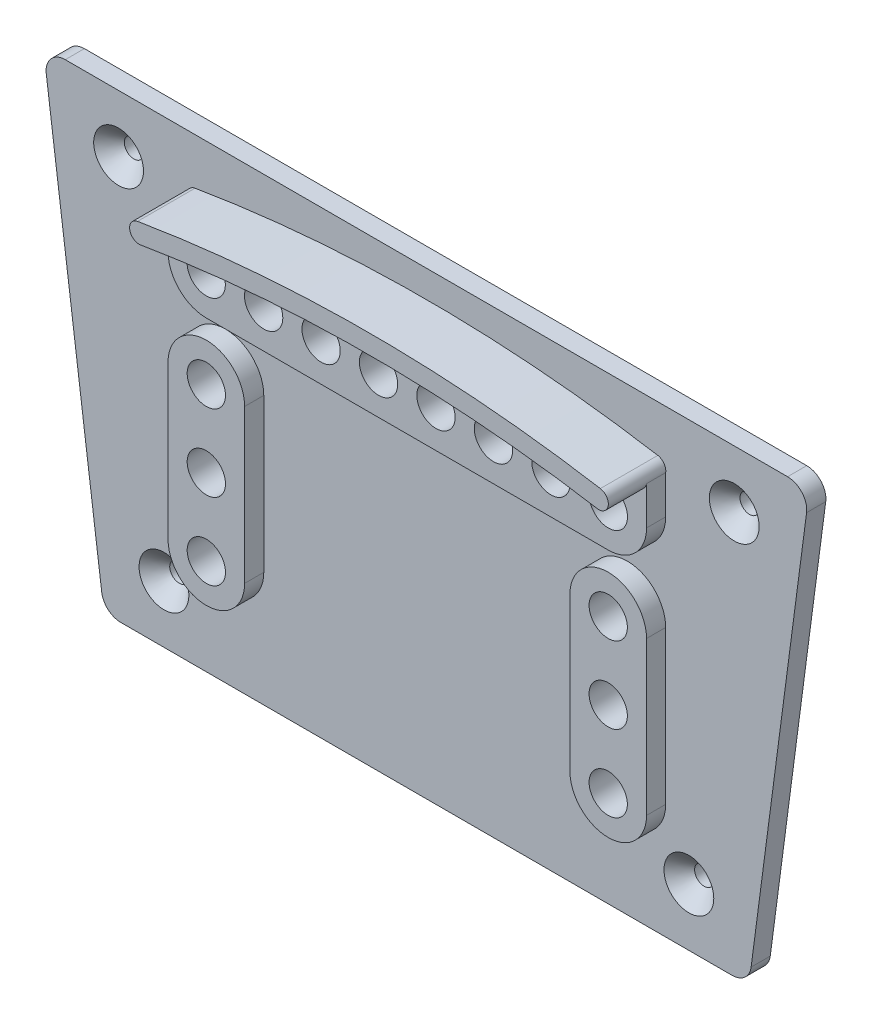
SolidWorks part; units mm, degrees
material "Nylon 101"
ref_plane "Front Plane" through (0, 0, 0) normal (0, 0, 1) x (1, 0, 0)
ref_plane "Top Plane" through (0, 0, 0) normal (0, 1, 0) x (1, 0, 0)
ref_plane "Right Plane" through (0, 0, 0) normal (1, 0, 0) x (0, 0, -1)
sketch "Sketch1" plane through (0, 0, 0) normal (0, 0, 1) x (1, 0, 0)
  line L1 (-53.4681, -38.1) -> (53.4681, -38.1)
  line L2 (-53.4681, -38.1) -> (-63.5, 38.1)
  line L3 (-63.5, 38.1) -> (63.5, 38.1)
  line L4 (53.4681, -38.1) -> (63.5, 38.1)
  line L5 (0, 38.1) -> (0, -38.1) construction
  line L6 (-58.484, 0) -> (58.484, 0) construction
  line L7 (-47.8993, -31.75) -> (47.8993, -31.75)
  line L8 (-47.8993, -31.75) -> (-56.2592, 31.75)
  line L9 (-56.2592, 31.75) -> (56.2592, 31.75)
  line L10 (47.8993, -31.75) -> (56.2592, 31.75)
  line L11 (0, 31.75) -> (0, -31.75) construction
  line L12 (-52.0792, 0) -> (52.0792, 0) construction
  point P0 (0, 0)
  point P4 (0, 0)
  dimension "D1" = 127
  dimension "D2" = 76.2
  dimension "D3" = 6.35
  dimension "D4" = 6.35
  dimension "D5" = 15
extrude "Boss-Extrude1" add sketch "Sketch1" along normal blind 3.175 contours L7 L10 L9 L8 | L1 L4 L3 L2 L10 L7 L8 L9 region at (-57.0156, 0.1933, 0) region at (0, 0.8494, 0)
extrude "Boss-Extrude2" add sketch "Sketch1<3>" against normal blind 3.175 contours L7 L10 L9 L8 region at (0, 0.8494, 0)
sketch "Sketch1<3>" plane through (0, 0, 0) normal (0, 0, 1) x (1, 0, 0) same geometry as "Sketch1"
sketch "Sketch2" plane through (0, 0, 0) normal (0, 0, 1) x (1, 0, 0)
  line L0 (-38.1, 28.8378) -> (0, 0) construction
  line L2 (0, 0) -> (38.1, 28.8378) construction
  line L4 (-33.3375, 22.225) -> (-23.8125, 22.225) construction
  line L5 (-39.6656, 28.575) -> (39.6656, 28.575) construction
  line L6 (-39.6656, 28.575) -> (-39.6656, 15.875)
  line L7 (-39.6656, 15.875) -> (39.6656, 15.875)
  line L8 (39.6656, 28.575) -> (39.6656, 15.875)
  line L9 (0, 22.225) -> (0, 0) construction
  line L10 (-33.3375, 22.225) -> (33.3375, 22.225) construction
  line L11 (-63.5, 38.1) -> (63.5, 38.1) construction
  arc A5 (-38.1, 28.8378) -> (38.1, 28.8378) centre (0, -198.1747) cw construction
  arc A6 (-37.8372, 27.2722) -> (37.8372, 27.2722) centre (0, -198.1747) cw
  arc A7 (-38.3628, 30.4034) -> (38.3628, 30.4034) centre (0, -198.1747) cw
  arc A8 (-37.8372, 27.2722) -> (-38.3628, 30.4034) centre (-38.1, 28.8378) cw
  arc A9 (37.8372, 27.2722) -> (38.3628, 30.4034) centre (38.1, 28.8378) ccw
  circle A10 centre (-33.3375, 22.225) radius 3.175
  circle A11 centre (-23.8125, 22.225) radius 3.175
  circle A12 centre (-14.2875, 22.225) radius 3.175
  circle A13 centre (-4.7625, 22.225) radius 3.175
  circle A14 centre (4.7625, 22.225) radius 3.175
  circle A15 centre (14.2875, 22.225) radius 3.175
  circle A16 centre (23.8125, 22.225) radius 3.175
  circle A17 centre (33.3375, 22.225) radius 3.175
  point P7 (0, 22.225)
  point P8 (39.6656, 22.225)
  point P9 (0, 32.0128)
  dimension "D1" = 15.875
  dimension "D3" = 3.175
  dimension "D4" = 1.5875
  dimension "D7" = 6.35
  dimension "D8" = 8
  dimension "D5" = 1.5875
  dimension "D2" = 76.2
  dimension "D6" = 12.7
  dimension "D9" = 9.525
extrude "Boss-Extrude3" add sketch "Sketch2" along normal blind 6.35 contours A9 A6 A8 L6 L7 L8 A17 A16 A15 A14 A13 A12 A11 A10 | A10 | A11 | A12 | A13 | A14 | A15 | A16 | A17 | A6 A9 A7 A8 region at (0, 22.7442, 0) region at (0, 30.8867, 0) region at (-33.3375, 22.225, 0) region at (-23.8125, 22.225, 0) region at (-14.2875, 22.225, 0) region at (-4.7625, 22.225, 0) region at (4.7625, 22.225, 0) region at (14.2875, 22.225, 0) region at (23.8125, 22.225, 0) region at (33.3375, 22.225, 0)
extrude "Boss-Extrude4" add sketch "Sketch2<3>" along normal blind 12.7 contours A6 A9 A7 A8 region at (0, 30.8867, 0)
sketch "Sketch2<3>" plane through (0, 0, 0) normal (0, 0, 1) x (1, 0, 0) same geometry as "Sketch2"
extrude "Cut-Extrude1" cut sketch "Sketch2<4>" against normal through all both and the other way through all contours A10 | A11 | A12 | A13 | A14 | A15 | A16 | A17 region at (-33.3375, 22.225, 0) region at (-23.8125, 22.225, 0) region at (-14.2875, 22.225, 0) region at (-4.7625, 22.225, 0) region at (4.7625, 22.225, 0) region at (14.2875, 22.225, 0) region at (23.8125, 22.225, 0) region at (33.3375, 22.225, 0)
sketch "Sketch2<4>" plane through (0, 0, 0) normal (0, 0, 1) x (1, 0, 0) same geometry as "Sketch2"
fillet "Fillet1" radius 6.35 2 edges at (39.6656, 15.875, 4.7625) (-39.6656, 15.875, 4.7625)
sketch "Sketch4" plane through (0, 0, 0) normal (0, 0, 1) x (1, 0, 0)
  line L0 (0, 0) -> (0, -19.05) construction
  line L1 (-33.3156, 6.35) -> (33.3156, 6.35) construction
  line L2 (-33.3156, 6.35) -> (-33.3156, -19.05) construction
  line L3 (-33.3156, -19.05) -> (33.3156, -19.05) construction
  line L4 (33.3156, 6.35) -> (33.3156, -19.05) construction
  line L5 (-63.5, 38.1) -> (63.5, 38.1) construction
  line L6 (-33.3156, 6.35) -> (-33.3156, -19.05) construction
  line L7 (-26.9656, 6.35) -> (-26.9656, -19.05)
  line L8 (-39.6656, 6.35) -> (-39.6656, -19.05)
  line L9 (33.3156, 6.35) -> (33.3156, -19.05) construction
  line L10 (39.6656, 6.35) -> (39.6656, -19.05)
  line L11 (26.9656, 6.35) -> (26.9656, -19.05)
  line L12 (-39.6656, 22.225) -> (-39.6656, 28.575) construction
  circle A0 centre (-33.3156, 6.35) radius 3.175
  circle A1 centre (-33.3156, -6.35) radius 3.175
  circle A2 centre (-33.3156, -19.05) radius 3.175
  circle A3 centre (33.3156, 6.35) radius 3.175
  circle A4 centre (33.3156, -6.35) radius 3.175
  circle A5 centre (33.3156, -19.05) radius 3.175
  arc A12 (-26.9656, 6.35) -> (-39.6656, 6.35) centre (-33.3156, 6.35) ccw
  arc A13 (-39.6656, -19.05) -> (-26.9656, -19.05) centre (-33.3156, -19.05) ccw
  arc A14 (39.6656, 6.35) -> (26.9656, 6.35) centre (33.3156, 6.35) ccw
  arc A15 (26.9656, -19.05) -> (39.6656, -19.05) centre (33.3156, -19.05) ccw
  point P4 (-33.3156, -6.35)
  point P22 (33.3156, -6.35)
  dimension "D1" = 6.35
  dimension "D5" = 3.175
  dimension "D2" = 12.7
  dimension "D3" = 31.75
extrude "Boss-Extrude5" add sketch "Sketch4" along normal blind 6.35
extrude "Cut-Extrude2" cut sketch "Sketch4<2>" along normal through all both and the other way through all contours A0 | A1 | A2 | A5 | A4 | A3 region at (-33.3156, 6.35, 0) region at (-33.3156, -6.35, 0) region at (-33.3156, -19.05, 0) region at (33.3156, 6.35, 0) region at (33.3156, -6.35, 0) region at (33.3156, -19.05, 0)
sketch "Sketch4<2>" plane through (0, 0, 0) normal (0, 0, 1) x (1, 0, 0) same geometry as "Sketch4"
extrude "Boss-Extrude6" add sketch "Sketch1<4>" against normal blind 38.1 separate body contours L1 L4 L3 L2 L10 L7 L8 L9 region at (-57.0156, 0.1933, 0)
sketch "Sketch1<4>" plane through (0, 0, 0) normal (0, 0, 1) x (1, 0, 0) same geometry as "Sketch1"
extrude "Boss-Extrude7" add sketch "Sketch1<5>" against normal blind 6.35 from surface contours L7 L10 L9 L8 | L1 L4 L3 L2 L10 L7 L8 L9 region at (-57.0156, 0.1933, 0) region at (0, 0.8494, 0) starting at face at (0, 0, -38.1)
sketch "Sketch1<5>" plane through (0, 0, 0) normal (0, 0, 1) x (1, 0, 0) same geometry as "Sketch1"
sketch "Sketch5" plane through (0, 0, 0) normal (0, 0, 1) x (1, 0, 0)
  line L1 (-43.5137, -28.575) -> (43.5137, -28.575) construction
  line L2 (-43.5137, -28.575) -> (-51.0376, 28.575) construction
  line L3 (-51.0376, 28.575) -> (51.0376, 28.575) construction
  line L4 (-47.8993, -31.75) -> (47.8993, -31.75)
  line L5 (47.8993, -31.75) -> (56.2592, 31.75)
  line L6 (56.2592, 31.75) -> (-56.2592, 31.75)
  line L7 (-56.2592, 31.75) -> (-47.8993, -31.75)
  line L8 (-47.8993, -31.75) -> (47.8993, -31.75)
  line L9 (47.8993, -31.75) -> (56.2592, 31.75)
  line L10 (56.2592, 31.75) -> (-56.2592, 31.75)
  line L11 (-56.2592, 31.75) -> (-47.8993, -31.75)
  line L12 (43.5137, -28.575) -> (51.0376, 28.575) construction
  line L13 (0, 28.575) -> (0, -28.575) construction
  line L14 (-47.2757, 0) -> (47.2757, 0) construction
  circle A0 centre (-51.0376, 28.575) radius 1.5875
  circle A1 centre (51.0376, 28.575) radius 1.5875
  circle A2 centre (43.5137, -28.575) radius 1.5875
  circle A3 centre (-43.5137, -28.575) radius 1.5875
  circle A4 centre (-51.0376, 28.575) radius 6.35
  circle A5 centre (-43.5137, -28.575) radius 6.35
  circle A6 centre (43.5137, -28.575) radius 6.35
  circle A7 centre (51.0376, 28.575) radius 6.35
  point P2 (0, 0)
  dimension "D2" = 4.7625
  dimension "D3" = 3.175
  dimension "D4" = 3.175
  dimension "D5" = 3.175
  dimension "D1" = 0
extrude "Boss-Extrude11" add sketch "Sketch5" against normal through all contours L11 A4 L10 A0 | L8 A5 L11 A3 | L9 A6 L8 A2 | L10 A7 L9 A1 region at (-48.1925, -28.3716, 0) region at (40.2325, -23.3147, 0) region at (-55.5866, 27.7891, 0) region at (47.0976, 23.7877, 0)
extrude "Cut-Extrude9" cut sketch "Sketch5<4>" along normal through all both and the other way through all contours A0 | A3 | A2 | A1 region at (-51.0376, 28.575, 0) region at (51.0376, 28.575, 0) region at (43.5137, -28.575, 0) region at (-43.5137, -28.575, 0)
sketch "Sketch5<4>" plane through (0, 0, 0) normal (0, 0, 1) x (1, 0, 0) same geometry as "Sketch5"
sketch "Sketch6" plane through (-2.7734, -465.2965, 0) normal (-0.9914, 0.1305, 0) x (0, 0, -1)
  line L0 (25.4, -469.3116) -> (0, -469.3116) construction
  line L1 (0, -430.8828) -> (0, -507.7403) construction
  line L4 (44.45, -430.8828) -> (44.45, -507.7403) construction
  circle A0 centre (25.4, -469.3116) radius 6.35
  dimension "D1" = 12.7
  dimension "D2" = 19.05
extrude "Cut-Extrude10" cut sketch "Sketch6" along normal up to next (6.35 mm away) and the other way through all contours A0
chamfer "Chamfer1" distance 2.54 angle 45 4 edges at (52.6251, 28.575, 3.175) (45.1012, -28.575, 3.175) (-41.9262, -28.575, 3.175) (-49.4501, 28.575, 3.175)
fillet "Fillet2" radius 3.175 8 edges at (0, -38.1, -44.45) (58.484, 0, -44.45) (0, 38.1, -44.45) (-58.484, 0, -44.45) (53.4681, -38.1, -22.225) (63.5, 38.1, -22.225) (-53.4681, -38.1, -22.225) (-63.5, 38.1, -22.225)
fillet "Fillet3" radius 3.175 4 edges at (-53.4681, -38.1, 1.5875) (-63.5, 38.1, 1.5875) (63.5, 38.1, 1.5875) (53.4681, -38.1, 1.5875)
delete or keep bodies "Body-Delete/Keep 1" type keep bodies bodies 111
